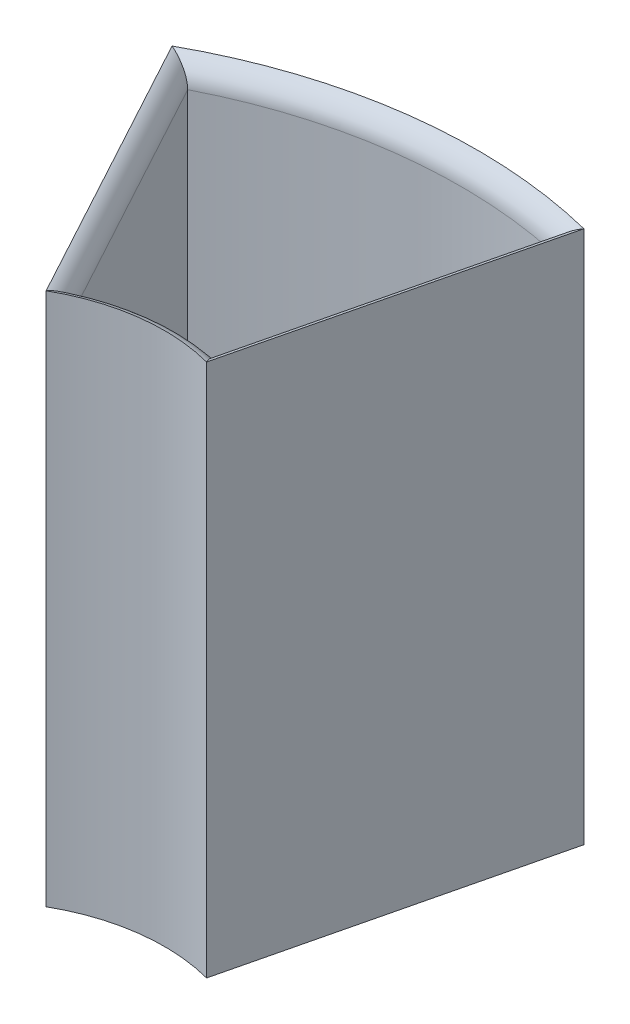
SolidWorks part; units mm, degrees
ref_plane "Front Plane" through (0, 0, 0) normal (0, 0, 1) x (1, 0, 0)
ref_plane "Top Plane" through (0, 0, 0) normal (0, 1, 0) x (1, 0, 0)
ref_plane "Right Plane" through (0, 0, 0) normal (1, 0, 0) x (0, 0, -1)
sketch "Sketch1" plane through (0, 0, 0) normal (0, 1, 0) x (1, 0, 0)
  line L0 (-10.561, 22.6598) -> (-26.774, 52.5752)
  line L1 (-11.3857, 19.9841) -> (-29.4936, 53.396)
  line L2 (5.8597, 22.241) -> (14.7598, 59.1874)
  line L3 (4.3742, 24.6144) -> (12.3429, 57.6945)
  arc A0 (14.7598, 59.1874) -> (-29.4936, 53.396) centre (0, 0) ccw
  arc A1 (5.8597, 22.241) -> (-11.3857, 19.9841) centre (0, 0) ccw
  arc A2 (12.3429, 57.6945) -> (-26.774, 52.5752) centre (0, 0) ccw
  arc A3 (4.3742, 24.6144) -> (-10.561, 22.6598) centre (0, 0) ccw
  dimension "D1" = 61
  dimension "D2" = 23
  dimension "D3" = 42
  dimension "D4" = 19.9841
  dimension "D5" = 59.1874
  dimension "D6" = 2
extrude "Boss-Extrude1" add sketch "Sketch1" along normal blind 2 contours L0 A2 L3 A3
extrude "Boss-Extrude2" add sketch "Sketch1<3>" along normal blind 65 contours A1 L2 A0 L1 L3 A3 L0 A2 region at (-19.9092, 0, -36.9775)
sketch "Sketch1<3>" plane through (0, 0, 0) normal (0, 1, 0) x (1, 0, 0) same geometry as "Sketch1"
fillet "Fillet1" radius 3 8 edges at (-18.6675, 2, -37.6175) (-3.2441, 2, -24.7886) (8.3585, 2, -41.1544) (-7.6561, 2, -58.5012) (-3.2441, 65, -24.7886) (-18.6675, 65, -37.6175) (8.3585, 65, -41.1544) (-7.6561, 65, -58.5012)
